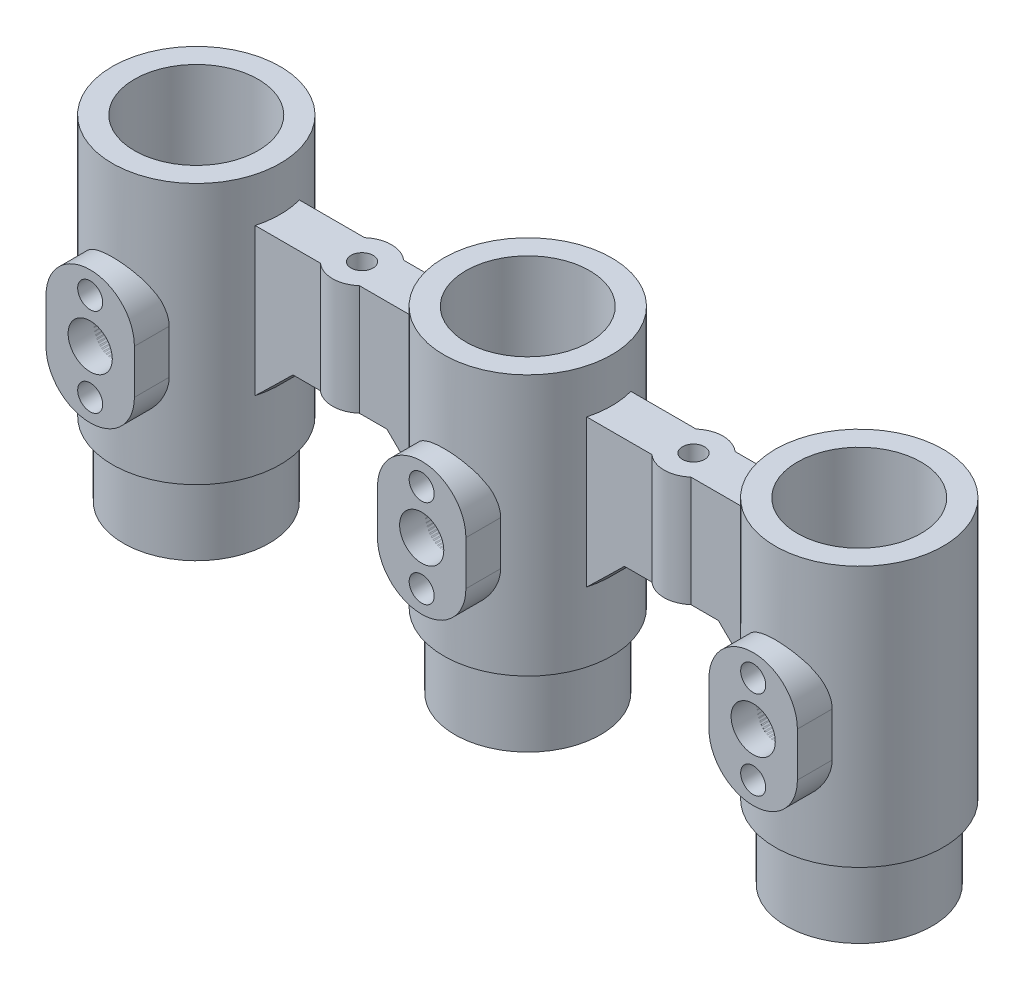
SolidWorks part; units mm, degrees
note: The reader was unsure of these and kept them because the rebuilt part matched: shared geometry of "Sketch1<5>", "Sketch1<6>", "Sketch16<8>".
ref_plane "Płaszczyzna przednia" through (0, 0, 0) normal (0, 0, 1) x (1, 0, 0)
ref_plane "Płaszczyzna górna" through (0, 0, 0) normal (0, 1, 0) x (1, 0, 0)
ref_plane "Płaszczyzna prawa" through (0, 0, 0) normal (1, 0, 0) x (0, 0, -1)
sketch "Sketch1" plane through (0, 0, 0) normal (0, 0, 1) x (1, 0, 0)
  line L0 (-11.4, 0) -> (0, 0) construction
  line L1 (-7.4, -4) -> (0, -4) construction
  line L2 (-11.4, 0) -> (-7.4, -4) construction
  line L4 (0, 51.1501) -> (0, -55.1326) construction
  line L12 (11.4, 14.5847) -> (11.4, 54)
  line L13 (8.4, 54) -> (8.4, 4.5847)
  line L14 (8.4, 54) -> (11.4, 54)
  line L15 (-29.798, -4) -> (0, -4) construction
  line L16 (45, 51.1501) -> (45, -55.1326) construction
  line L20 (53.4, 54) -> (53.4, 4.5847)
  line L21 (56.4, 14.5847) -> (56.4, 54)
  line L22 (53.4, 54) -> (56.4, 54)
  line L23 (-45, 51.1501) -> (-45, -55.1326) construction
  line L24 (7.4, -4) -> (34.28, -4) construction
  line L26 (-33.6, 14.5847) -> (-33.6, 54)
  line L28 (-36.6, 54) -> (-36.6, 4.5847)
  line L29 (-36.6, 54) -> (-33.6, 54)
  line L48 (-36.6, 14.5847) -> (-33.6, 14.5847)
  line L49 (8.4, 14.5847) -> (8.4, 4.5847)
  line L50 (-35.1, 14.5847) -> (-33.6, 14.5847)
  line L54 (-36.6, 14.5847) -> (-35.1, 14.5847)
  line L55 (-36.6, 14.5847) -> (-36.6, 4.5847)
  line L56 (-36.6, 4.5847) -> (-35.1, 4.5847)
  line L57 (-35.1, 14.5847) -> (-35.1, 4.5847)
  line L58 (8.4, 14.5847) -> (9.9, 14.5847)
  line L59 (9.9, 14.5847) -> (9.9, 4.5847)
  line L60 (8.4, 4.5847) -> (9.9, 4.5847)
  line L61 (8.4, 14.5847) -> (11.4, 14.5847)
  line L62 (53.4, 14.5847) -> (53.4, 4.5847)
  line L63 (53.4, 14.5847) -> (54.9, 14.5847)
  line L64 (54.9, 14.5847) -> (54.9, 4.5847)
  line L65 (53.4, 4.5847) -> (54.9, 4.5847)
  line L66 (53.4, 14.5847) -> (56.4, 14.5847)
  point P3 (0, 0)
  dimension "D3" = 4
  dimension "D6" = 3
  dimension "D7" = 2
  dimension "D13" = 39.4153
  dimension "D14" = 10
  dimension "D15" = 1.5
  dimension "D16" = 3
  dimension "D8" = 2
revolve "Revolve2" add sketch "Sketch1" angle 360 about L4
ref_plane "Plane1" through (0, 44, 0) normal (0, 1, 0) x (1, 0, 0)
revolve "Revolve3" add sketch "Sketch1<5>" angle 360 about L23
sketch "Sketch1<5>" plane through (0, 0, 0) normal (0, 0, 1) x (1, 0, 0) same geometry as "Sketch1"
revolve "Revolve4" add sketch "Sketch1<6>" angle 360 about L16
sketch "Sketch1<6>" plane through (0, 0, 0) normal (0, 0, 1) x (1, 0, 0) same geometry as "Sketch1"
sketch "Sketch2" plane through (0, 44, 0) normal (0, 1, 0) x (1, 0, 0)
  line L0 (-41.602, 0) -> (10.9982, 0) construction
  line L1 (0, 22.4384) -> (0, -20.7049) construction
  line L3 (10.9982, 3) -> (10.9982, -3)
  line L12 (19.8542, 3) -> (10.9982, 3)
  line L13 (10.9982, 3) -> (10.9982, -3)
  line L14 (19.8542, -3) -> (10.9982, -3)
  line L15 (34.0018, -3) -> (25.1458, -3)
  line L16 (34.0018, 3) -> (34.0018, -3)
  line L21 (34.0018, 3) -> (25.1458, 3)
  line L22 (-10.9982, 3) -> (-34.0018, -3) construction
  line L23 (-25.1458, 3) -> (-34.0018, 3)
  line L26 (-25.1458, -3) -> (-34.0018, -3)
  line L30 (-34.0018, 3) -> (-34.0018, -3)
  line L31 (-10.9982, -3) -> (-19.8542, -3)
  line L32 (-10.9982, 3) -> (-10.9982, -3)
  line L33 (-10.9982, 3) -> (-19.8542, 3)
  circle A1 centre (0, 0) radius 11.4 construction
  arc A5 (-21.9933, 3.9678) -> (-19.8542, 3) centre (-22.5, 0) cw
  arc A6 (-21.9933, 1.4118) -> (-23.0067, 1.4118) centre (-22.5, 0) cw
  circle A8 centre (-22.5, 0) radius 1.5
  arc A9 (-25.1458, 3) -> (-23.0067, 3.9678) centre (-22.5, 0) cw
  arc A10 (-25.1458, -3) -> (-19.8542, -3) centre (-22.5, 0) ccw
  arc A12 (-19.8542, -3) -> (-25.1458, -3) centre (-22.5, 0) cw
  arc A13 (-19.8542, 3) -> (-25.1458, 3) centre (-22.5, 0) ccw
  arc A14 (19.8542, -3) -> (25.1458, -3) centre (22.5, 0) ccw
  arc A15 (23.0067, 3.9678) -> (25.1458, 3) centre (22.5, 0) cw
  arc A16 (25.1458, 3) -> (19.8542, 3) centre (22.5, 0) ccw
  circle A17 centre (22.5, 0) radius 1.5
  point P3 (0, 0)
  point P15 (22.5, 0)
  point P48 (-22.5, 0)
  dimension "D2" = 2
  dimension "D3" = 2
  dimension "D1" = 6
extrude "Boss-Extrude1" add sketch "Sketch2" against normal blind 15
sketch "Sketch9" plane through (0, 54, 0) normal (0, 1, 0) x (1, 0, 0)
  line L1 (-82.1677, 43.8182) -> (84.2185, 43.8182)
  line L2 (-82.1677, 43.8182) -> (-82.1677, -46.6893)
  line L3 (-82.1677, -46.6893) -> (84.2185, -46.6893)
  line L4 (84.2185, 43.8182) -> (84.2185, -46.6893)
extrude "Cut-Extrude1" cut sketch "Sketch9" against normal blind 4
chamfer "Chamfer1" distance 5 angle 45 4 edges at (-11.4, 29, 0) (-33.6, 29, 0) (11.4, 29, 0) (33.6, 29, 0)
ref_plane "Plane2" through (0, 0, 11.4) normal (0, 0, 1) x (1, 0, 0)
sketch "Sketch14" plane through (0, 50, 0) normal (0, 1, 0) x (1, 0, 0)
  circle A0 centre (45, 0) radius 8.4
  circle A1 centre (45, 0) radius 8.4 construction
sketch "Sketch15" plane through (0, 0, 0) normal (0, 0, 1) x (1, 0, 0)
  line L0 (45, 50) -> (45, 13.0243) construction
sketch "Sketch16" plane through (0, 0, 11.4) normal (0, 0, 1) x (1, 0, 0)
  line L0 (45, 50) -> (45, 13.0243) construction
  line L1 (53.4, 50) -> (36.6, 50) construction
  line L2 (45, 41.5563) -> (45, 18.5012) construction
  line L3 (39, 33) -> (39, 27)
  line L4 (51, 33) -> (51, 27)
  circle A0 centre (45, 30) radius 3
  circle A4 centre (45, 36) radius 1.7
  circle A5 centre (45, 24) radius 1.7
  arc A8 (43.3171, 24.2408) -> (46.6829, 24.2408) centre (45, 30) ccw
  arc A10 (46.6829, 35.7592) -> (43.3171, 35.7592) centre (45, 30) ccw
  circle A11 centre (45, 27) radius 6
  circle A12 centre (45, 33) radius 6
  dimension "D1" = 6
  dimension "D3" = 6
  dimension "D4" = 6
  dimension "D9" = 12
  dimension "D10" = 12
  dimension "D2" = 20
extrude "Boss-Extrude9" add sketch "Sketch16" along normal mid plane 6 separate body contours L2 A12 A11 A5 | A12 L3 A11 | L2 A12 A11 A4 | A11 A12 A0 | A12 L2 A5 A11 | A0 A12 A11 | A12 L2 A4 A11 | A12 A11 L4
extrude "Cut-Extrude7" cut sketch "Sketch16<8>" against normal blind 10 contours A0 L2 | L2 A0 | A4 L2 A10 | L2 A4 A10 | A10 L2 A4 | L2 A10 A4 | A5 L2 A8 | A8 L2 A5 | L2 A5 A8 | L2 A8 A5
sketch "Sketch16<8>" plane through (0, 0, 11.4) normal (0, 0, 1) x (1, 0, 0) same geometry as "Sketch16"
pattern_linear "LPattern11" count 3 spacing 45 along (-1, 0, 0) of "Boss-Extrude9", "Cut-Extrude7"
sketch "Sketch12" plane through (0, 50, 0) normal (0, 1, 0) x (1, 0, 0)
  line L0 (4.3651, 0) -> (118.2028, 0) construction
  line L4 (56.1336, 2.45) -> (64.8344, 2.45)
  line L5 (56.1336, 2.45) -> (56.1336, -2.45)
  line L6 (56.1336, -2.45) -> (64.8344, -2.45)
  arc A0 (64.8344, -2.45) -> (64.8344, 2.45) centre (72.45, 0) ccw
  arc A1 (47.45, -17) -> (47.45, 17) centre (47.45, 0) ccw construction
  circle A4 centre (45, 0) radius 11.4 construction
  point P4 (56.1336, 0)
  dimension "D1" = 16
  dimension "D2" = 4.9
extrude "Boss-Extrude6" [suppressed] add sketch "Sketch12" against normal blind 6
fillet "Fillet10" [suppressed] radius 7
sketch "Sketch5" plane through (0, 29, 0) normal (0, -1, 0) x (-1, 0, 0)
  circle A0 centre (22.5, 0) radius 7
  arc A1 (29.2082, -2) -> (29.2082, 2) centre (22.5, 0) ccw construction
  circle A2 centre (-22.5, 0) radius 7
  dimension "D1" = 2
extrude "Boss-Extrude3" [suppressed] add sketch "Sketch5" along normal blind 5.7
sketch "Sketch6" [suppressed] plane through (0, 23.3, 0) normal (0, -1, 0) x (-1, 0, 0)
  circle A0 centre (22.5, 0) radius 7
  circle A1 centre (22.5, 0) radius 2.6
  circle A3 centre (22.5, 0) radius 7 construction
  circle A4 centre (-22.5, 0) radius 7
  circle A5 centre (-22.5, 0) radius 2.6
  dimension "D1" = 5.2
  dimension "D2" = 2
extrude "Boss-Extrude4" [suppressed] add sketch "Sketch6" along normal blind 1.5
